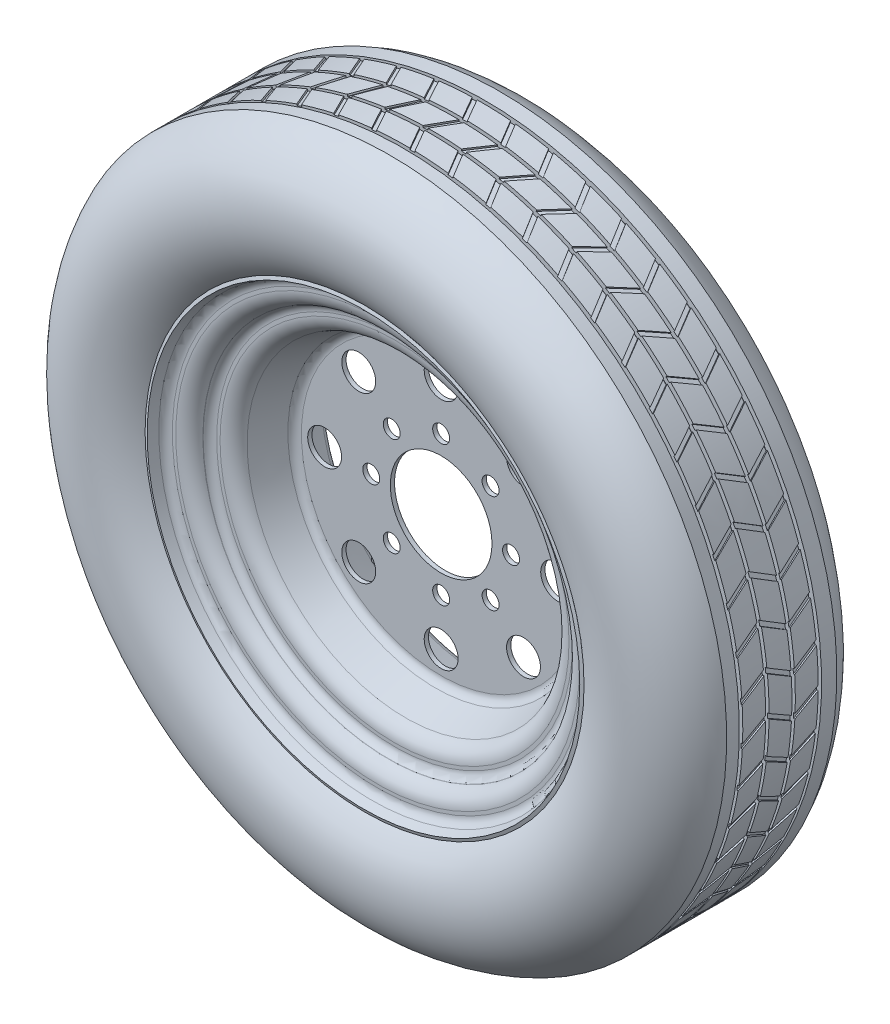
SolidWorks part; units mm, degrees
ref_plane "Front" through (0, 0, 0) normal (0, 0, 1) x (1, 0, 0)
ref_plane "Top" through (0, 0, 0) normal (0, 1, 0) x (1, 0, 0)
ref_plane "Right" through (0, 0, 0) normal (1, 0, 0) x (0, 0, -1)
sketch "Sketch1" plane through (0, 0, 0) normal (1, 0, 0) x (0, 0, -1)
  line L0 (0, 0) -> (0, 386.7163) construction
  line L1 (0, 60) -> (0, 164.9197)
  line L2 (9.8697, 179.0151) -> (45.1303, 191.8489)
  line L3 (55, 205.9443) -> (55, 209.9381)
  line L4 (64.8697, 224.0335) -> (65.1303, 224.1283)
  line L5 (75, 238.2237) -> (75, 242.2175)
  line L6 (84.8697, 256.3129) -> (95, 260)
  line L7 (-84.8697, 256.3129) -> (-95, 260)
  line L8 (-75, 238.2237) -> (-75, 242.2175)
  line L9 (-64.8697, 224.0335) -> (-65.1303, 224.1283)
  line L10 (-55, 205.9443) -> (-55, 209.9381)
  line L11 (-9.8697, 179.0151) -> (-45.1303, 191.8489)
  line L12 (-11.5798, 174.3166) -> (-46.8404, 187.1505)
  line L13 (-60, 205.9443) -> (-60, 209.9381)
  line L14 (-66.5798, 219.335) -> (-66.8404, 219.4299)
  line L15 (-80, 238.2237) -> (-80, 242.2175)
  line L16 (-86.5798, 251.6144) -> (-96.7101, 255.3015)
  line L17 (8.1596, 183.7136) -> (43.4202, 196.5474)
  line L18 (50, 205.9443) -> (50, 209.9381)
  line L19 (63.1596, 228.7319) -> (63.4202, 228.8268)
  line L20 (70, 238.2237) -> (70, 242.2175)
  line L21 (83.1596, 261.0113) -> (93.2899, 264.6985)
  line L22 (-5, 164.9197) -> (-5, 60)
  line L23 (-5, 60) -> (0, 60)
  line L24 (-95, 260) -> (-96.7101, 255.3015)
  line L25 (93.2899, 264.6985) -> (95, 260)
  line L26 (-156.9465, 0) -> (207.3997, 0) construction
  arc A0 (0, 164.9197) -> (9.8697, 179.0151) centre (15, 164.9197) cw
  arc A1 (45.1303, 191.8489) -> (55, 205.9443) centre (40, 205.9443) ccw
  arc A2 (55, 209.9381) -> (64.8697, 224.0335) centre (70, 209.9381) cw
  arc A3 (65.1303, 224.1283) -> (75, 238.2237) centre (60, 238.2237) ccw
  arc A4 (75, 242.2175) -> (84.8697, 256.3129) centre (90, 242.2175) cw
  arc A5 (-75, 242.2175) -> (-84.8697, 256.3129) centre (-90, 242.2175) ccw
  arc A6 (-65.1303, 224.1283) -> (-75, 238.2237) centre (-60, 238.2237) cw
  arc A7 (-55, 209.9381) -> (-64.8697, 224.0335) centre (-70, 209.9381) ccw
  arc A8 (-45.1303, 191.8489) -> (-55, 205.9443) centre (-40, 205.9443) cw
  arc A9 (-2.9167, 173.8075) -> (-9.8697, 179.0151) centre (-15, 164.9197) ccw
  arc A10 (-5, 164.9197) -> (-11.5798, 174.3166) centre (-15, 164.9197) ccw
  arc A11 (-46.8404, 187.1505) -> (-60, 205.9443) centre (-40, 205.9443) cw
  arc A12 (-60, 209.9381) -> (-66.5798, 219.335) centre (-70, 209.9381) ccw
  arc A13 (-66.8404, 219.4299) -> (-80, 238.2237) centre (-60, 238.2237) cw
  arc A14 (-80, 242.2175) -> (-86.5798, 251.6144) centre (-90, 242.2175) ccw
  arc A15 (-2.9167, 173.8075) -> (8.1596, 183.7136) centre (15, 164.9197) cw
  arc A16 (43.4202, 196.5474) -> (50, 205.9443) centre (40, 205.9443) ccw
  arc A17 (50, 209.9381) -> (63.1596, 228.7319) centre (70, 209.9381) cw
  arc A18 (63.4202, 228.8268) -> (70, 238.2237) centre (60, 238.2237) ccw
  arc A19 (70, 242.2175) -> (83.1596, 261.0113) centre (90, 242.2175) cw
  arc A20 (0, 164.9197) -> (-9.8697, 179.0151) centre (-15, 164.9197) ccw construction
  arc A21 (-5, 164.9197) -> (8.1596, 183.7136) centre (15, 164.9197) cw construction
  point P12 (0, 175.4228)
  point P15 (55, 195.4412)
  point P18 (55, 220.4412)
  point P21 (75, 227.7206)
  point P24 (75, 252.7206)
  point P40 (-75, 252.7206)
  point P41 (-75, 227.7206)
  point P42 (-55, 220.4412)
  point P43 (-55, 195.4412)
  dimension "D9" = 15
  dimension "D1" = 60
  dimension "D2" = 200
  dimension "D3" = 95
  dimension "D4" = 25
  dimension "D5" = 25
  dimension "D6" = 110
  dimension "D7" = 20
  dimension "D8" = 20
  dimension "D10" = 5
revolve "Revolve1" add sketch "Sketch1" angle 360 about L26
sketch "Sketch3" plane through (0, 0, 0) normal (0, 0, -1) x (-1, 0, 0)
  circle A0 centre (0, 0) radius 137.5 construction
  circle A1 centre (0, 137.5) radius 20
  circle A2 centre (97.2272, 97.2272) radius 20
  circle A3 centre (137.5, 0) radius 20
  circle A4 centre (97.2272, -97.2272) radius 20
  circle A5 centre (0, -137.5) radius 20
  circle A6 centre (-97.2272, -97.2272) radius 20
  circle A7 centre (-137.5, 0) radius 20
  circle A8 centre (-97.2272, 97.2272) radius 20
  point P21 (0, 0)
  dimension "D1" = 275
  dimension "D2" = 40
  dimension "D3" = 8
extrude "Cut-Extrude1" cut sketch "Sketch3" against normal mid plane 20
sketch "Sketch4" plane through (0, 0, 5) normal (0, 0, 1) x (1, 0, 0)
  circle A0 centre (0, 0) radius 82.5 construction
  circle A1 centre (0, 82.5) radius 10
  circle A2 centre (58.3363, 58.3363) radius 10
  circle A3 centre (82.5, 0) radius 10
  circle A4 centre (58.3363, -58.3363) radius 10
  circle A5 centre (0, -82.5) radius 10
  circle A6 centre (-58.3363, -58.3363) radius 10
  circle A7 centre (-82.5, 0) radius 10
  circle A8 centre (-58.3363, 58.3363) radius 10
  point P22 (0, 0)
  dimension "D1" = 165
  dimension "D2" = 20
  dimension "D3" = 8
extrude "Cut-Extrude2" cut sketch "Sketch4" against normal blind 20
ref_axis "Axis1" through (0, 0, -126.9336) along (0, 0, 1)
sketch "Sketch5" plane through (0, 0, 0) normal (1, 0, 0) x (0, 0, -1)
  line L0 (-65, 397) -> (65, 397)
  line L1 (83.1596, 261.0113) -> (93.2899, 259.4481)
  line L2 (93.2899, 264.6985) -> (93.2899, -264.6985) construction
  line L3 (-85.1351, 256.4095) -> (-95, 258.5717)
  line L4 (0, 0) -> (0, 625.4464) construction
  line L5 (-84.8697, 256.3129) -> (-95, 260) construction
  line L6 (-95, 260) -> (-95, -260) construction
  line L7 (84.9897, 272.871) -> (88.4241, 272.341)
  line L8 (-62.4321, 385) -> (62.2853, 385)
  line L9 (-82.5659, 268.1312) -> (-88.539, 269.4404)
  line L10 (-82.5659, 268.1312) -> (-85.1351, 256.4095)
  line L11 (84.9897, 272.871) -> (83.1596, 261.0113)
  arc A0 (65, 397) -> (93.2899, 259.4481) centre (28.8289, 317.8757) cw
  arc A1 (-65, 397) -> (-95, 258.5717) centre (-30.6152, 317.0832) ccw
  arc A2 (62.2853, 385) -> (88.4241, 272.341) centre (28.8289, 317.8757) cw
  arc A3 (-62.4321, 385) -> (-88.539, 269.4404) centre (-30.6152, 317.0832) ccw
  dimension "D4" = 75
  dimension "D5" = 75
  dimension "D1" = 130
  dimension "D2" = 12
  dimension "D3" = 385
revolve "Revolve2" add sketch "Sketch5" angle 360 about axis through (0, 0, -126.9336) along (0, 0, 1)
sketch "Sketch6" plane through (0, 0, 0) normal (1, 0, 0) x (0, 0, -1)
  line L1 (65, 397) -> (-65, 397) construction
  line L2 (-50, 397) -> (-46, 397)
  line L3 (-50, 397) -> (-50, 390)
  line L4 (-50, 390) -> (-46, 390)
  line L6 (-46, 397) -> (-46, 390)
  line L7 (-65, 397) -> (-65, -397) construction
  line L8 (-19, 397) -> (-15, 397)
  line L9 (-19, 397) -> (-19, 390)
  line L10 (-19, 390) -> (-15, 390)
  line L11 (-15, 397) -> (-15, 390)
  line L12 (12, 397) -> (16, 397)
  line L13 (12, 397) -> (12, 390)
  line L14 (12, 390) -> (16, 390)
  line L15 (16, 397) -> (16, 390)
  line L16 (43, 397) -> (47, 397)
  line L17 (43, 397) -> (43, 390)
  line L18 (43, 390) -> (47, 390)
  line L19 (47, 397) -> (47, 390)
  dimension "D1" = 4
  dimension "D2" = 4
  dimension "D3" = 4
  dimension "D4" = 4
  dimension "D5" = 7
  dimension "D6" = 7
  dimension "D7" = 7
  dimension "D8" = 7
  dimension "D9" = 27
  dimension "D10" = 27
  dimension "D11" = 27
  dimension "D12" = 15
revolve "Cut-Revolve1" cut sketch "Sketch6" angle 360 about axis through (0, 0, -126.9336) along (0, 0, 1)
ref_plane "Plane1" through (400, 0, 0) normal (1, 0, 0) x (0, 0, -1)
sketch "Sketch7" plane through (400, 0, 0) normal (1, 0, 0) x (0, 0, -1)
  line L0 (43, 0) -> (16, -15.5885)
  line L1 (43, -390) -> (43, 390) construction
  line L2 (16, 397) -> (16, -397) construction
  line L3 (12, -15.5885) -> (-15, 0)
  line L4 (-46, -15.5885) -> (-46, -21.362)
  line L6 (12, -390) -> (12, 390) construction
  line L7 (-19, 0) -> (-19, -5.7735)
  line L8 (-46, 390) -> (-46, -390) construction
  line L9 (-46, -15.5885) -> (47, -15.5885) construction
  line L10 (47, 390) -> (47, -390) construction
  line L11 (-15, 390) -> (-15, -390) construction
  line L12 (-46, -15.5885) -> (-19, 0)
  line L13 (-19, -397) -> (-19, 397) construction
  line L14 (43, -5.7735) -> (16, -21.362)
  line L15 (12, -21.362) -> (-15, -5.7735)
  line L16 (-46, -21.362) -> (-19, -5.7735)
  line L17 (-15, 0) -> (-15, -5.7735)
  line L19 (12, -15.5885) -> (12, -21.362)
  line L20 (43, 0) -> (43, -5.7735)
  line L22 (16, -15.5885) -> (16, -21.362)
  line L23 (45.5, -4.3301) -> (18.5, -19.9186) construction
  line L24 (9.5, -19.9186) -> (-17.5, -4.3301) construction
  line L25 (-43.5, -19.9186) -> (-16.5, -4.3301) construction
  dimension "D1" = 30
  dimension "D2" = 30
  dimension "D3" = 30
  dimension "D4" = 5
  dimension "D5" = 5
extrude "Cut-Extrude4" cut sketch "Sketch7" against normal blind 5
pattern_circular "CirPattern1" count 55 over 360 about axis through (0, 0, -126.9336) along (0, 0, 1) of "Cut-Extrude4"
